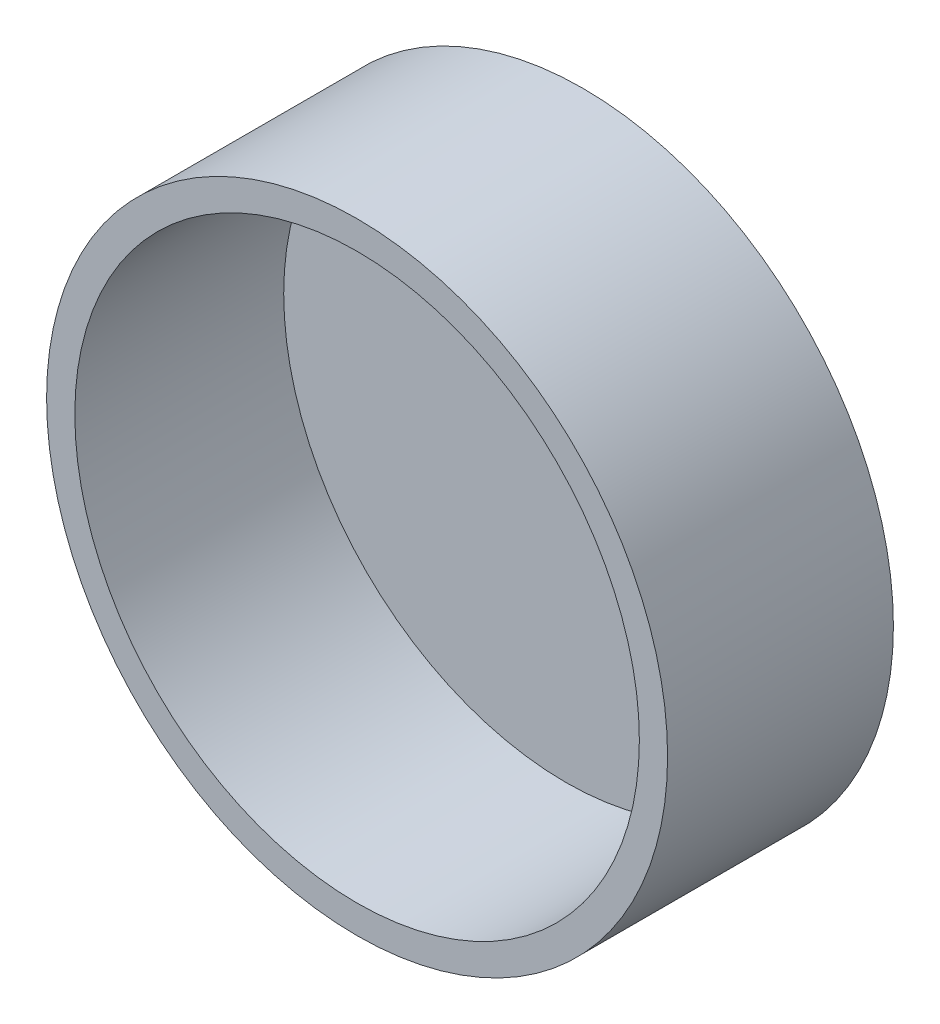
SolidWorks part; units mm, degrees
ref_plane "Front Plane" through (0, 0, 0) normal (0, 0, 1) x (1, 0, 0)
ref_plane "Top Plane" through (0, 0, 0) normal (0, 1, 0) x (1, 0, 0)
ref_plane "Right Plane" through (0, 0, 0) normal (1, 0, 0) x (0, 0, -1)
sketch "Sketch1" plane through (0, 0, 0) normal (0, 0, 1) x (1, 0, 0)
  line L0 (0, 65) -> (50, 65)
  line L1 (0, 65) -> (-50, 65)
  circle A0 centre (0, 0) radius 100
  circle A1 centre (0, 0) radius 110
  circle A3 centre (0, 65) radius 14
  circle A6 centre (0, 65) radius 17
  circle A9 centre (-41.1218, 65) radius 6.7
  circle A10 centre (41.1218, 65) radius 6.9
  circle A11 centre (-41.1218, 65) radius 10
  circle A12 centre (41.1218, 65) radius 10
  circle A13 centre (0, 65) radius 10.75
  circle A14 centre (-41.1218, 65) radius 3
extrude "Boss-Extrude1" add sketch "Sketch1" along normal blind 6 contours A0 A12 A6 A11 | L1 A6 L0 A3 | L0 A6 L1 A3 | A12 A10 | A11 A9 region at (0, 79.3801, 0) region at (15.5, 64.6199, 0) region at (41.1218, 74.7172, 0) region at (-50.839, 65, 0) region at (0, -3.3419, 0)
extrude "Boss-Extrude2" add sketch "Sketch1<3>" along normal blind 80 contours A1 A0 region at (-106.8887, 0, 0)
sketch "Sketch1<3>" plane through (0, 0, 0) normal (0, 0, 1) x (1, 0, 0) same geometry as "Sketch1"
extrude "Boss-Extrude3" add sketch "Sketch1<10>" against normal blind 5 contours A12 A10 | L0 A6 L1 A3 | L1 A6 L0 A3 | A11 A9 | A14 L1 A9 | A14 L1 A9 | A13 L0 A3 L1 | A13 L1 A3 L0 region at (0, 76.063, 0) region at (12.375, 64.687, 0) region at (0, 79.3801, 0) region at (15.5, 64.6199, 0) region at (41.1218, 74.7172, 0) region at (-41.1218, 61.7626, 0) region at (-41.1218, 68.2374, 0) region at (-50.839, 65, 0)
sketch "Sketch1<10>" plane through (0, 0, 0) normal (0, 0, 1) x (1, 0, 0) same geometry as "Sketch1"
